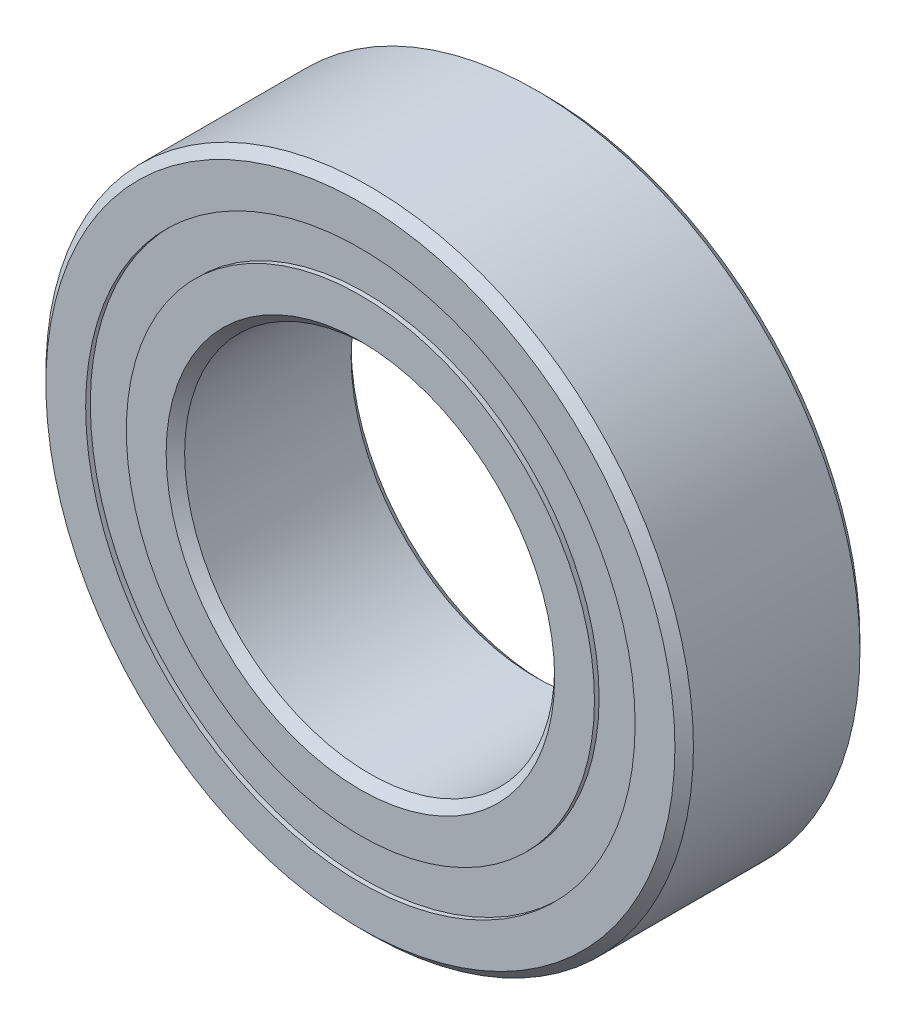
SolidWorks part; units mm, degrees
ref_plane "Front Plane" through (0, 0, 0) normal (0, 0, 1) x (1, 0, 0)
ref_plane "Top Plane" through (0, 0, 0) normal (0, 1, 0) x (1, 0, 0)
ref_plane "Right Plane" through (0, 0, 0) normal (1, 0, 0) x (0, 0, -1)
sketch "Sketch1" plane through (0, 0, 0) normal (1, 0, 0) x (0, 0, -1)
  line L0 (-2, 0) -> (2, 0) construction
  line L1 (0, 7) -> (0, -7) construction
  line L2 (1.8, 7) -> (-1.8, 7)
  line L3 (-1.8, 7) -> (-2, 6.8)
  line L4 (-2, 6.8) -> (-2, 5.9396)
  line L5 (-2, 5.9396) -> (-0.8889, 5.9396)
  line L6 (2, 5.9396) -> (0.8889, 5.9396)
  line L7 (2, 6.8) -> (2, 5.9396)
  line L8 (1.8, 7) -> (2, 6.8)
  line L9 (0, 7) -> (0, 5.5) construction
  line L10 (0, 5.5) -> (0, 4) construction
  arc A0 (-0.8889, 5.9396) -> (0.8889, 5.9396) centre (0, 5.5) cw
  point P14 (0, 4)
  dimension "Width" = 4
  dimension "OD" = 14
  dimension "D1" = 45
  dimension "D2" = 0.2
  dimension "Shaft Dia" = 8
  dimension "D3" = 1.7778
  dimension "D4" = 0.4396
revolve "Revolve1" add sketch "Sketch1" angle 360 about L0
sketch "Sketch3" plane through (0, 0, 0) normal (1, 0, 0) x (0, 0, -1)
  line L0 (-2, 5.0604) -> (-0.8889, 5.0604)
  line L1 (0, 7) -> (0, -7) construction
  line L2 (-2, 6.8) -> (-2, 5.9396) construction
  line L3 (-2, 5.0604) -> (-2, 4.2)
  line L4 (-1.8, 7) -> (-2, 6.8) construction
  line L5 (-2, 4.2) -> (-1.8, 4)
  line L6 (-1.8, 4) -> (1.8, 4)
  line L7 (1.8, 7) -> (1.8, -7) construction
  line L8 (1.8, 4) -> (2, 4.2)
  line L9 (2, -6.8) -> (2, 6.8) construction
  line L10 (2, 4.2) -> (2, 5.0604)
  line L11 (2, 5.0604) -> (0.8889, 5.0604)
  line L13 (1.8, 7) -> (2, 6.8) construction
  arc A0 (0.8889, 5.9396) -> (-0.8889, 5.9396) centre (0, 5.5) ccw construction
  arc A1 (0.8889, 5.0604) -> (-0.8889, 5.0604) centre (0, 5.5) cw
revolve "Revolve3" add sketch "Sketch3" angle 360 about L0
sketch "Sketch4" plane through (0, 0, 0) normal (1, 0, 0) x (0, 0, -1)
  line L0 (-0.9916, 5.5) -> (0.9916, 5.5)
  arc A2 (-0.9916, 5.5) -> (0.9916, 5.5) centre (0, 5.5) cw
  arc A3 (0.8889, 5.9396) -> (-0.8889, 5.9396) centre (0, 5.5) ccw construction
revolve "Revolve4" add sketch "Sketch4" angle 360 about L0
ref_axis "Axis1" through (0, 0, -2) along (0, 0, 1)
pattern_circular "CirPattern1" count 12 every 30 about axis through (0, 0, -2) along (0, 0, 1) of bodies 104
sketch "Sketch5" plane through (0, 0, 0) normal (1, 0, 0) x (0, 0, -1)
  line L0 (-2, 5.9396) -> (-0.8889, 5.9396) construction
  line L1 (-1.9, 5.9396) -> (-0.9916, 5.9396)
  line L2 (-1.9, 5.9396) -> (-1.9, 5.0604)
  line L3 (-1.9, 5.0604) -> (-0.9916, 5.0604)
  line L4 (-0.9916, 5.9396) -> (-0.9916, 5.0604)
  line L5 (-2, 5.0604) -> (-0.8889, 5.0604) construction
  line L6 (2, 5.9396) -> (0.8889, 5.9396) construction
  line L7 (1.9, 5.9396) -> (0.9916, 5.9396)
  line L8 (1.9, 5.9396) -> (1.9, 5.0604)
  line L9 (1.9, 5.0604) -> (0.9916, 5.0604)
  line L10 (0.9916, 5.9396) -> (0.9916, 5.0604)
  line L11 (2, 5.0604) -> (0.8889, 5.0604) construction
  line L12 (-1.8, 7) -> (-2, 6.8) construction
  point P18 (-1.9, 6.9)
revolve "Revolve5" add sketch "Sketch5" angle 360 about L0
sketch "Sketch6" plane through (0, 0, 0) normal (1, 0, 0) x (0, 0, -1)
  line L0 (2, 0) -> (-2, 0) construction
  line L1 (2, 5.9396) -> (0.9, 5.9396)
  line L2 (2, 5.9396) -> (2, 9.5)
  line L3 (2, 9.5) -> (0.9, 9.5)
  line L4 (0.9, 5.9396) -> (0.9, 9.5)
  dimension "Th" = 1.1
  dimension "Flange OD" = 19
revolve "Revolve6" [suppressed] add sketch "Sketch6" angle 360 about L0
ref_axis "Axis2" through (0, 0, -1.8) along (0, 0, 1)
ref_plane "Plane1" through (0, 0, -2) normal (0, 0, -1) x (-1, 0, 0)
ref_plane "Plane2" through (0, 0, 2) normal (0, 0, 1) x (1, 0, 0)
equation "\"D2@Sketch1\" = \"Width@Sketch1\"*.05"
equation "\"D3@Sketch1\" = \"Width@Sketch1\"/2.25"
equation "\"D4@Sketch1\" = (((\"OD@Sketch1\"-\"Width@Sketch1\")/2)/3.25)/3.5"
equation "\"D2@CirPattern1\" = 360/\"Balls@CirPattern1\""
